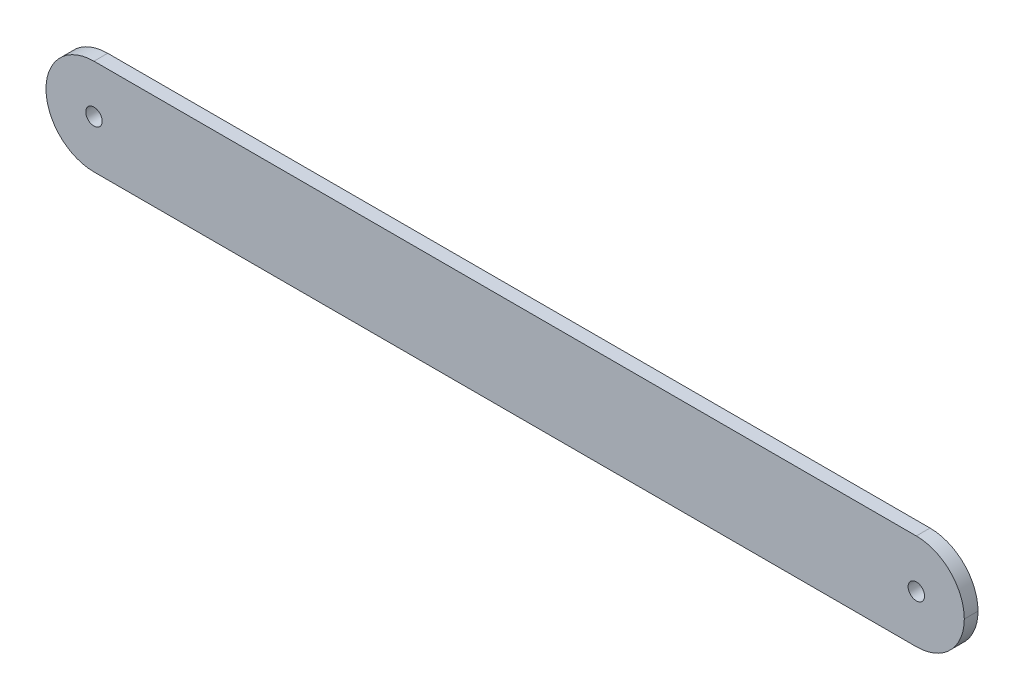
SolidWorks part; units mm, degrees
ref_plane "Front Plane" through (0, 0, 0) normal (0, 0, 1) x (1, 0, 0)
ref_plane "Top Plane" through (0, 0, 0) normal (0, 1, 0) x (1, 0, 0)
ref_plane "Right Plane" through (0, 0, 0) normal (1, 0, 0) x (0, 0, -1)
sketch "Sketch1" plane through (0, 0, 0) normal (0, 0, 1) x (1, 0, 0)
  line L1 (-335, -35) -> (335, -35)
  line L2 (-335, -35) -> (-335, 35)
  line L3 (-335, 35) -> (335, 35)
  line L4 (335, -35) -> (335, 35)
  line L5 (-335, -35) -> (335, 35) construction
  line L6 (-335, 35) -> (335, -35) construction
  point P0 (0, 0)
  dimension "D1" = 670
  dimension "D2" = 70
extrude "Boss-Extrude1" add sketch "Sketch1" along normal blind 10
sketch "Sketch2" plane through (0, 0, 10) normal (0, 0, 1) x (1, 0, 0)
  line L2 (-335, -35) -> (335, -35) construction
  circle A0 centre (-300, 0) radius 6
  circle A1 centre (300, 0) radius 6
  dimension "D2" = 12
  dimension "D3" = 12
  dimension "D1" = 35
  dimension "D4" = 35
  dimension "D5" = 300
  dimension "D6" = 300
extrude "Cut-Extrude1" cut sketch "Sketch2" against normal through all
fillet "Fillet1" radius 35 4 edges at (335, -35, 5) (335, 35, 5) (-335, -35, 5) (-335, 35, 5)
